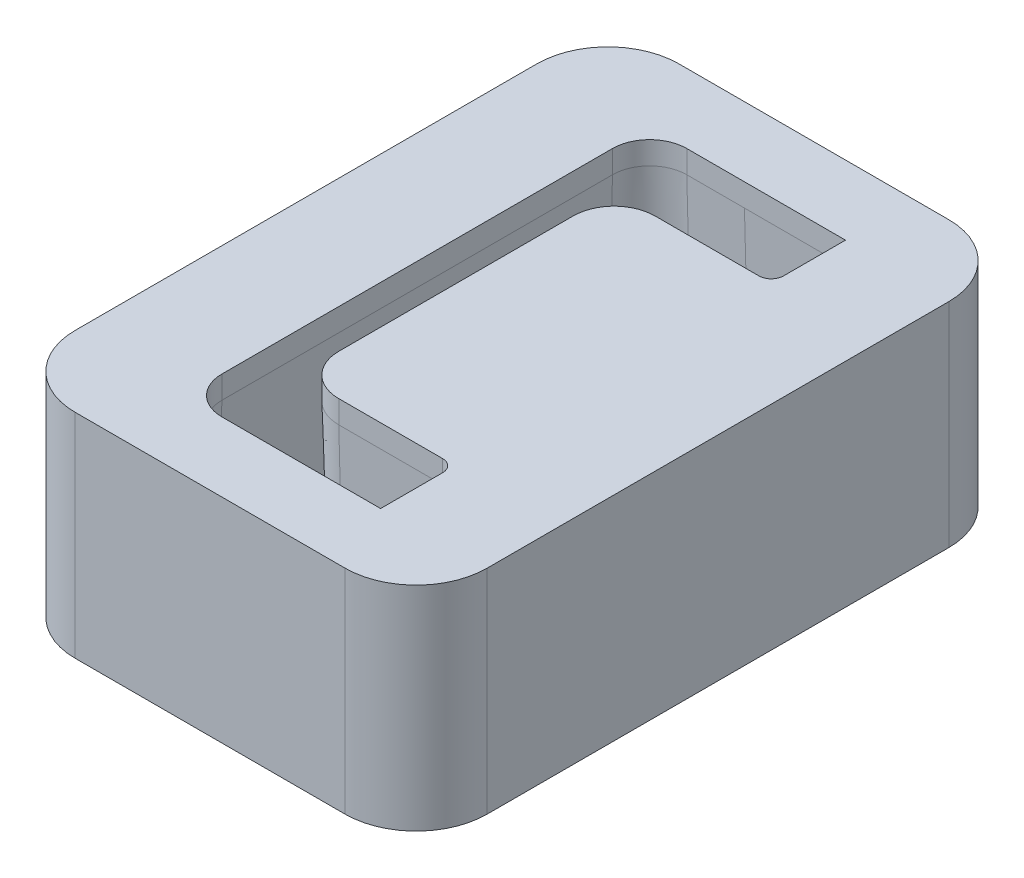
SolidWorks part; units mm, degrees
material "K110"
ref_plane "Front Plane" through (0, 0, 0) normal (0, 0, 1) x (1, 0, 0)
ref_plane "Top Plane" through (0, 0, 0) normal (0, 1, 0) x (1, 0, 0)
ref_plane "Right Plane" through (0, 0, 0) normal (1, 0, 0) x (0, 0, -1)
sketch "Sketch1" plane through (0, 0, 0) normal (0, 1, 0) x (1, 0, 0)
  line L1 (-29, -42.5) -> (29, -42.5)
  line L2 (-29, -42.5) -> (-29, 42.5)
  line L3 (-29, 42.5) -> (29, 42.5)
  line L4 (29, -42.5) -> (29, 42.5)
  line L5 (-29, -42.5) -> (29, 42.5) construction
  line L6 (-29, 42.5) -> (29, -42.5) construction
  point P0 (0, 0)
  dimension "D1" = 85
  dimension "D2" = 58
extrude "Boss-Extrude1" add sketch "Sketch1" against normal blind 30
fillet "Fillet1" radius 10 4 edges at (-29, -15, -42.5) (29, -15, -42.5) (29, -15, 42.5) (-29, -15, 42.5)
sketch "Sketch2" plane through (0, 0, 0) normal (0, 1, 0) x (1, 0, 0)
  line L16 (14.23, 32.73) -> (-8.12, 32.73)
  line L17 (-13.35, 27.5) -> (-13.35, -27.5)
  line L18 (-8.12, -32.73) -> (14.23, -32.73)
  line L19 (14.23, -32.73) -> (14.23, -24)
  line L20 (12.5, -22.27) -> (-2.12, -22.27)
  line L21 (-7.89, -16.5) -> (-7.89, 16.5)
  line L22 (-2.12, 22.27) -> (12.5, 22.27)
  line L23 (14.23, 24) -> (14.23, 32.73)
  line L24 (14.23, 32.73) -> (-8.12, 32.73)
  line L25 (-13.35, 27.5) -> (-13.35, -27.5)
  line L26 (-8.12, -32.73) -> (14.23, -32.73)
  line L27 (14.23, -32.73) -> (14.23, -24)
  line L28 (12.5, -22.27) -> (-2.12, -22.27)
  line L29 (-7.89, -16.5) -> (-7.89, 16.5)
  line L30 (-2.12, 22.27) -> (12.5, 22.27)
  line L31 (14.23, 24) -> (14.23, 32.73)
  arc A12 (-8.12, 32.73) -> (-13.35, 27.5) centre (-8.12, 27.5) ccw
  arc A13 (-13.35, -27.5) -> (-8.12, -32.73) centre (-8.12, -27.5) ccw
  arc A14 (14.23, -24) -> (12.5, -22.27) centre (12.5, -24) ccw
  arc A15 (-7.89, -16.5) -> (-2.12, -22.27) centre (-2.12, -16.5) ccw
  arc A16 (-2.12, 22.27) -> (-7.89, 16.5) centre (-2.12, 16.5) ccw
  arc A17 (12.5, 22.27) -> (14.23, 24) centre (12.5, 24) ccw
  arc A18 (-8.12, 32.73) -> (-13.35, 27.5) centre (-8.12, 27.5) ccw
  arc A19 (-13.35, -27.5) -> (-8.12, -32.73) centre (-8.12, -27.5) ccw
  arc A20 (14.23, -24) -> (12.5, -22.27) centre (12.5, -24) ccw
  arc A21 (-7.89, -16.5) -> (-2.12, -22.27) centre (-2.12, -16.5) ccw
  arc A22 (-2.12, 22.27) -> (-7.89, 16.5) centre (-2.12, 16.5) ccw
  arc A23 (12.5, 22.27) -> (14.23, 24) centre (12.5, 24) ccw
  dimension "D1" = 0.23
extrude "Cut-Extrude1" cut sketch "Sketch2" against normal up to next
sketch "Sketch3" plane through (0, 0, 0) normal (1, 0, 0) x (0, 0, -1)
  line L0 (32.73, -3.2) -> (33.4318, -30)
  line L1 (32.73, -30) -> (32.73, 0) construction
  line L2 (32.5, -30) -> (42.5, -30) construction
  line L3 (33.4318, -30) -> (32.73, -30)
  line L4 (32.73, -30) -> (32.73, -3.2)
  line L5 (31.9, 0) -> (-31.9, 0) construction
  dimension "D1" = 3.2
  dimension "D2" = 1.5
sketch "Sketch5" plane through (0, 0, 0) normal (0, 1, 0) x (1, 0, 0)
  line L0 (12.5, -22.27) -> (-2.12, -22.27) construction
  line L1 (14.23, -32.73) -> (14.23, -24) construction
  line L2 (-8.12, -32.73) -> (14.23, -32.73) construction
  line L3 (-7.89, -16.5) -> (-7.89, 16.5) construction
  line L4 (-2.12, 22.27) -> (12.5, 22.27) construction
  line L5 (-13.35, 27.5) -> (-13.35, -27.5) construction
  line L6 (14.23, 32.73) -> (-8.12, 32.73) construction
  line L7 (14.23, 24) -> (14.23, 32.73) construction
  line L8 (12.5, -22.27) -> (-2.12, -22.27)
  line L9 (14.23, -32.73) -> (14.23, -24)
  line L10 (-8.12, -32.73) -> (14.23, -32.73)
  line L11 (-7.89, -16.5) -> (-7.89, 16.5)
  line L12 (-2.12, 22.27) -> (12.5, 22.27)
  line L13 (-13.35, 27.5) -> (-13.35, -27.5)
  line L14 (14.23, 32.73) -> (-8.12, 32.73)
  line L15 (14.23, 24) -> (14.23, 32.73)
  arc A0 (-7.89, -16.5) -> (-2.12, -22.27) centre (-2.12, -16.5) ccw construction
  arc A1 (14.23, -24) -> (12.5, -22.27) centre (12.5, -24) ccw construction
  arc A2 (-13.35, -27.5) -> (-8.12, -32.73) centre (-8.12, -27.5) ccw construction
  arc A3 (-2.12, 22.27) -> (-7.89, 16.5) centre (-2.12, 16.5) ccw construction
  arc A4 (-8.12, 32.73) -> (-13.35, 27.5) centre (-8.12, 27.5) ccw construction
  arc A5 (12.5, 22.27) -> (14.23, 24) centre (12.5, 24) ccw construction
  arc A6 (-7.89, -16.5) -> (-2.12, -22.27) centre (-2.12, -16.5) ccw
  arc A7 (14.23, -24) -> (12.5, -22.27) centre (12.5, -24) ccw
  arc A8 (-13.35, -27.5) -> (-8.12, -32.73) centre (-8.12, -27.5) ccw
  arc A9 (-2.12, 22.27) -> (-7.89, 16.5) centre (-2.12, 16.5) ccw
  arc A10 (-8.12, 32.73) -> (-13.35, 27.5) centre (-8.12, 27.5) ccw
  arc A11 (12.5, 22.27) -> (14.23, 24) centre (12.5, 24) ccw
sweep "Cut-Sweep1" cut profiles "Sketch3" path "Sketch5"
hole_wizard "M6 Tapped Hole1" positions "Sketch8" profile "Sketch7" tap size "M6" standard "ISO"
sketch "Sketch8" plane through (0, -30, 0) normal (0, -1, 0) x (-1, 0, 0)
  line L0 (-19, 42.5) -> (19, 42.5) construction
  line L1 (-29, -32.5) -> (-29, 32.5) construction
  line L2 (29, 32.5) -> (29, -32.5) construction
  line L3 (19, -42.5) -> (-19, -42.5) construction
  point P0 (-22, 35.5)
  point P2 (22, 35.5)
  point P4 (22, -35.5)
  point P6 (-22, -35.5)
  point P9 (0, 0)
  point P10 (0, 0)
  point P11 (0, 0)
  point P12 (0, 0)
  dimension "D1" = 7
  dimension "D2" = 7
  dimension "D3" = 7
  dimension "D4" = 7
sketch "Sketch7" plane through (22, -30, -35.5) normal (1, 0, 0) x (0, 0, -1)
  line L0 (0, 0) -> (0, 18.5022)
  line L1 (0, 18.5022) -> (2.5, 17)
  line L2 (2.5, 17) -> (2.5, 0.525)
  line L3 (2.5, 0.525) -> (3.025, 0)
  line L5 (3.025, 0) -> (0, 0)
  line L6 (-2.5, 0.525) -> (-3.025, 0) construction
  line L10 (0, 18.5022) -> (-2.5, 17) construction
  line L11 (0, -6.35) -> (0, 107.95) construction
  dimension "Tap Drill Dia." = 5
  dimension "Tap Drill Depth" = 17
  dimension "Near C'Sink Dia." = 6.05
  dimension "Near C'Sink Angle" = 90
  dimension "Drill Angle" = 118
cosmetic thread "Hole Thread1"
cosmetic thread "Hole Thread2"
cosmetic thread "Hole Thread3"
cosmetic thread "Hole Thread4"
